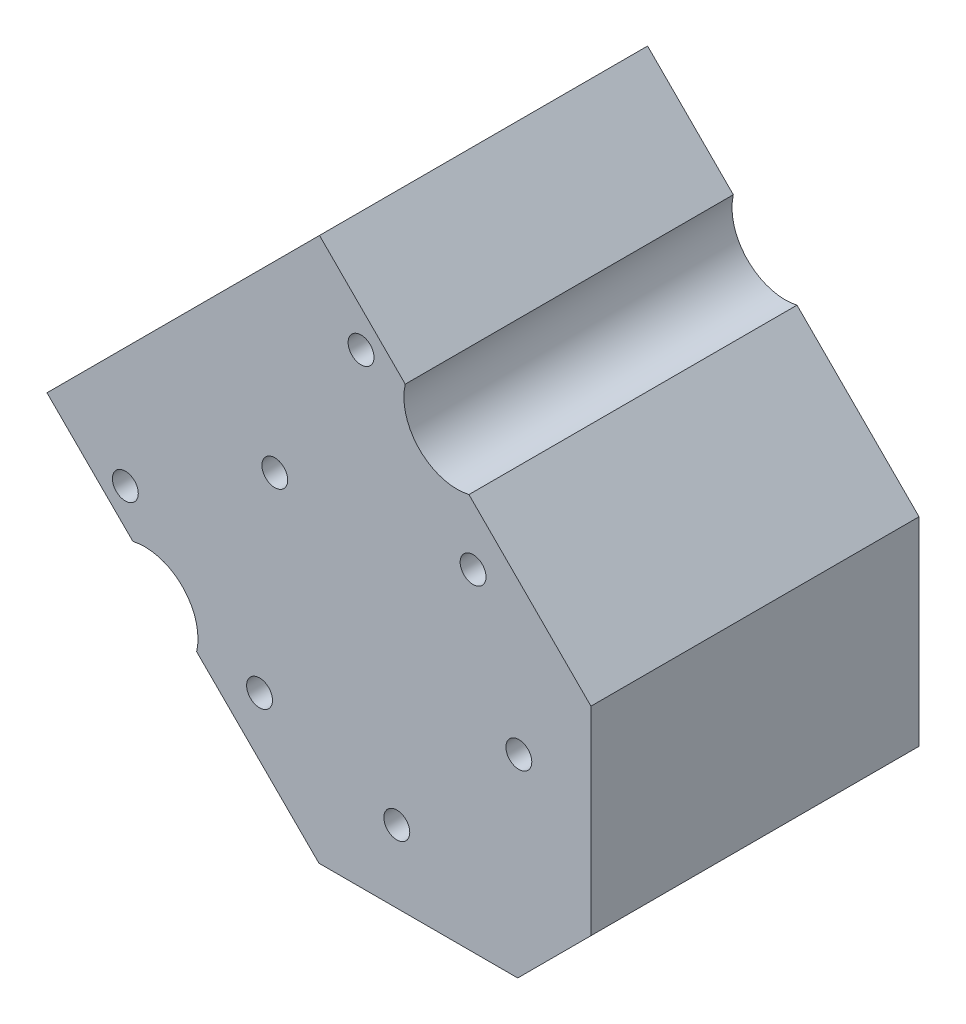
SolidWorks part; units mm, degrees
ref_plane "Front Plane" through (0, 0, 0) normal (0, 0, 1) x (1, 0, 0)
ref_plane "Top Plane" through (0, 0, 0) normal (0, 1, 0) x (1, 0, 0)
ref_plane "Right Plane" through (0, 0, 0) normal (1, 0, 0) x (0, 0, -1)
sketch "Sketch1" plane through (0, 0, 0) normal (0, 0, 1) x (1, 0, 0)
  line L0 (0, 0) -> (0, 73.5) construction
  line L1 (-96.5, -48) -> (-73.5, -48) construction
  line L2 (-96.5, -48) -> (-96.5, 52) construction
  line L4 (-73.5, -48) -> (-73.5, 27) construction
  line L5 (-52, 96.5) -> (48, 96.5) construction
  line L7 (-27, 73.5) -> (48, 73.5) construction
  line L8 (48, 96.5) -> (48, 73.5) construction
  line L9 (0, 0) -> (-73.5, 0) construction
  line L10 (-27, 73.5) -> (-73.5, 27) construction
  line L11 (-73.5, 73.5) -> (-27, 73.5) construction
  line L12 (-73.5, 27) -> (-73.5, 73.5) construction
  line L13 (-58.4584, 90.0416) -> (-90.0416, 58.4584)
  line L14 (-96.5, 96.5) -> (-52, 96.5) construction
  line L15 (-96.5, 52) -> (-96.5, 96.5) construction
  line L16 (-24.3179, 73.5) -> (-25, 73.5) construction
  line L17 (23.2069, 73.5) -> (48, 73.5) construction
  line L18 (-73.5, 25) -> (-73.5, 24.3179) construction
  line L19 (-73.5, -48) -> (-73.5, -23.2069) construction
  line L20 (-73.5, 23.2069) -> (-73.5, -23.2069) construction
  line L21 (-23.2069, 73.5) -> (23.2069, 73.5) construction
  line L22 (-58.5251, 27) -> (-35.4853, 27)
  line L23 (-27, 35.4853) -> (-27, 58.5251)
  line L24 (-35.4853, 27) -> (-27, 35.4853)
  line L25 (-25, 73.5) -> (-27, 73.5) construction
  line L26 (-27, 71.5) -> (-27, 73.5) construction
  line L27 (-73.5, 27) -> (-73.5, 25) construction
  line L28 (-73.5, 27) -> (-71.5, 27) construction
  line L29 (-23.2069, 73.5) -> (-24.3179, 73.5) construction
  line L30 (-73.5, 24.3179) -> (-73.5, 23.2069) construction
  line L31 (-27, 71.5) -> (-27, 73.5) construction
  line L32 (-27, 96.5) -> (-52, 96.5) construction
  line L33 (-71.5, 27) -> (-73.5, 27) construction
  line L34 (-96.5, 52) -> (-96.5, 27) construction
  line L35 (-27, 58.5251) -> (-41.1411, 72.6923)
  line L36 (-52, 96.5) -> (-58.4584, 90.0416) construction
  line L37 (-27, 73.5) -> (-27, 96.5) construction
  line L38 (-27, 58.5251) -> (-27, 71.5) construction
  line L39 (0, 0) -> (-80.9943, 80.9943) construction
  line L40 (-58.5251, 27) -> (-72.6923, 41.1411)
  line L41 (-71.5, 27) -> (-58.5251, 27) construction
  line L42 (-90.0416, 58.4584) -> (-96.5, 52) construction
  line L43 (-73.5, 27) -> (-96.5, 27) construction
  line L44 (-48.5208, 80.0857) -> (-58.4584, 90.0416)
  line L47 (-80.0857, 48.5208) -> (-90.0416, 58.4584)
  line L48 (-66.0195, 34.4805) -> (-80.0857, 48.5208) construction
  line L49 (-72.6923, 41.1411) -> (-66.0195, 34.4805) construction
  arc A0 (23.2069, 73.5) -> (-22.3981, 74.1947) centre (0, 47.3) ccw construction
  arc A1 (-74.1947, 22.3981) -> (-73.5, -23.2069) centre (-47.3, 0) ccw construction
  arc A2 (-25, 73.5) -> (-27, 71.5) centre (-25, 71.5) ccw construction
  arc A3 (-71.5, 27) -> (-73.5, 25) centre (-71.5, 25) ccw construction
  arc A4 (-24.3179, 73.5) -> (-22.3981, 74.1947) centre (-24.3179, 76.5) ccw construction
  arc A5 (-22.3981, 74.1947) -> (-23.2069, 73.5) centre (0, 47.3) ccw construction
  arc A6 (-73.5, 24.3179) -> (-74.1947, 22.3981) centre (-76.5, 24.3179) cw construction
  arc A7 (-73.5, 23.2069) -> (-74.1947, 22.3981) centre (-47.3, 0) ccw construction
  arc A8 (-48.5208, 80.0857) -> (-41.1411, 72.6923) centre (-42.503, 78.7127) ccw
  arc A9 (-80.0857, 48.5208) -> (-72.6923, 41.1411) centre (-78.7127, 42.503) cw
  dimension "D6" = 35
  dimension "D10" = 2
  dimension "D11" = 3
  dimension "D1" = 135
  dimension "D2" = 23
  dimension "D3" = 73.5
  dimension "D4" = 48
  dimension "D8" = 27
  dimension "D9" = 12
  dimension "D5" = 100
  dimension "D7" = 26.2
extrude "Boss-Extrude1" add sketch "Sketch1" along normal blind 38.0226
ref_axis "Axis1" through (0, 0, -0.2) along (0, 0, 1)
sketch "Sketch4" plane through (0, 0, 38.0226) normal (0, 0, 1) x (1, 0, 0)
  line L0 (0, 0) -> (0, 52.0101) construction
  line L1 (0, 0) -> (-63.6396, 63.6396) construction
  line L2 (0, 0) -> (-52.0101, 0) construction
  line L5 (-80.9601, 53.6396) -> (-63.6396, 63.6396) construction
  line L6 (-63.6396, 63.6396) -> (-83.2677, 83.2677) construction
  line L8 (-65.4074, 40.6586) -> (-40.6586, 65.4074) construction
  line L9 (-35.3553, 49.4975) -> (-49.4975, 35.3553) construction
  line L11 (-35.4853, 27) -> (-27, 35.4853) construction
  circle A1 centre (-63.6396, 63.6396) radius 1.5
  circle A3 centre (-80.9601, 53.6396) radius 1.5
  circle A4 centre (-53.6396, 80.9601) radius 1.5
  circle A9 centre (-40.6586, 65.4074) radius 1.5
  circle A10 centre (-65.4074, 40.6586) radius 1.5
  circle A11 centre (-49.4975, 35.3553) radius 1.5
  circle A12 centre (-35.3553, 49.4975) radius 1.5
  dimension "D2" = 20
  dimension "D3" = 3
  dimension "D1" = 45
  dimension "D6" = 45.8162
  dimension "D7" = 75
  dimension "D9" = 35
  dimension "D10" = 20
  dimension "D11" = 15
  dimension "D12" = 15
extrude "Cut-Extrude2" cut sketch "Sketch4" against normal through all
equation "\"EyeDiameter\" = 35"
equation "\"BasePlaneDistance\" = \"EyeDiameter\"/2+19.84"
equation "\"EyeClearance\" = 2"
equation "\"L2Thickness\" = 8"
equation "\"L2_ID\" = 20"
equation "\"Offset\"= - 2"
equation "\"D3@Sketch1\"=\"BasePlaneDistance\" + 38.16 +\"Offset\""
equation "\"D7@Sketch1\"=24.20 - \"Offset\""
equation "\"D2@Sketch1\"=25.00 + \"Offset\""
